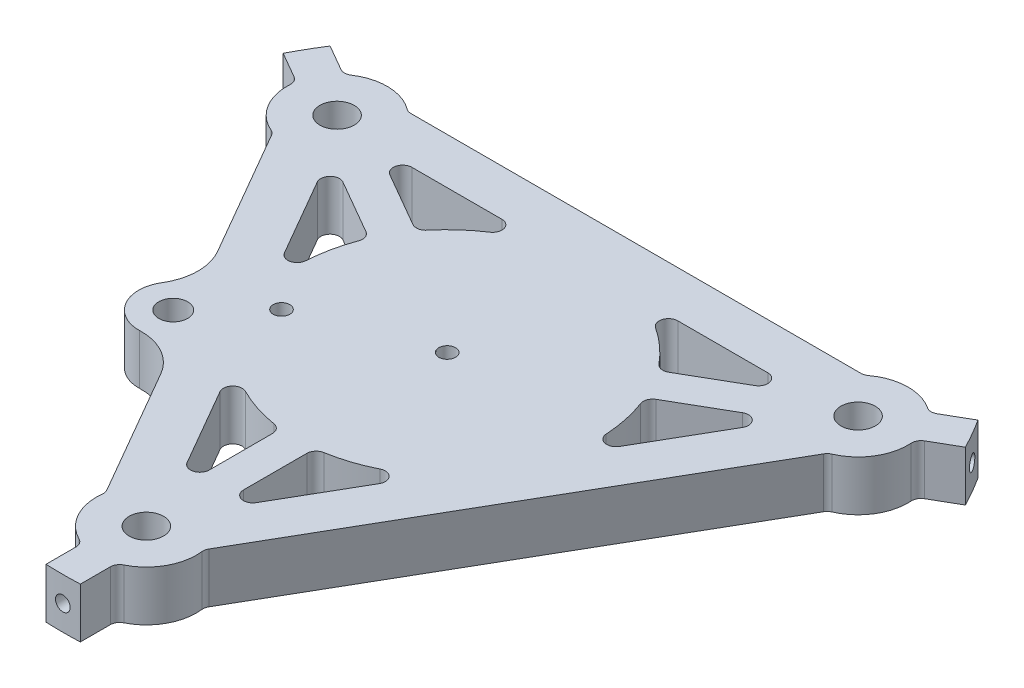
SolidWorks part; units mm, degrees
material "ABS"
ref_plane "Front Plane" through (0, 0, 0) normal (0, 0, 1) x (1, 0, 0)
ref_plane "Top Plane" through (0, 0, 0) normal (0, 1, 0) x (1, 0, 0)
ref_plane "Right Plane" through (0, 0, 0) normal (1, 0, 0) x (0, 0, -1)
sketch "Sketch1" plane through (0, 0, 0) normal (0, 1, 0) x (1, 0, 0)
  line L0 (-3.2639, -67.2662) -> (-3.2639, -72.952)
  line L1 (3.2639, -67.2662) -> (3.2639, -72.952)
  line L2 (3.2639, -41.9471) -> (3.2639, -29.9313)
  line L3 (-3.2639, -41.9471) -> (-3.2639, -29.9313)
  line L4 (-34.6953, 23.8002) -> (-24.2893, 17.7923)
  line L5 (-37.9592, 18.1469) -> (-27.5532, 12.139)
  line L6 (-56.6223, 36.4597) -> (-61.5464, 39.3026)
  line L7 (-59.8862, 30.8065) -> (-64.8103, 33.6494)
  line L8 (37.9592, 18.1469) -> (27.5532, 12.139)
  line L9 (34.6953, 23.8002) -> (24.2893, 17.7923)
  line L10 (59.8862, 30.8065) -> (64.8103, 33.6494)
  line L11 (56.6223, 36.4597) -> (61.5464, 39.3026)
  line L12 (0, 0) -> (0, -57.15) construction
  line L13 (0, 0) -> (-49.4934, 28.575) construction
  line L14 (0, 0) -> (49.4934, 28.575) construction
  line L15 (40.388, 15.7181) -> (31.8393, 0.9115)
  line L16 (9.6892, -54.9694) -> (52.4495, 19.0936)
  line L17 (-6.5817, -42.8361) -> (-15.1303, -28.0294)
  line L18 (-52.4495, 19.0936) -> (-9.6892, -54.9694)
  line L19 (-42.7603, 35.8758) -> (42.7603, 35.8758)
  line L20 (-33.8063, 27.118) -> (-16.709, 27.118)
  line L21 (16.709, 27.118) -> (33.8063, 27.118)
  line L22 (-31.8393, 0.9115) -> (-40.388, 15.7181)
  line L23 (15.1303, -28.0294) -> (6.5817, -42.8361)
  arc A0 (-3.2639, -72.952) -> (3.2639, -72.952) centre (0, 0) ccw
  arc A1 (4.7466, -28.178) -> (12.7944, -25.5506) centre (0, 0) ccw
  arc A2 (-9.4626, -56.0616) -> (-4.2488, -65.6749) centre (0, -57.15) ccw
  circle A3 centre (0, -57.15) radius 3.2639
  arc A4 (4.2488, -65.6749) -> (9.4626, -56.0616) centre (0, -57.15) ccw
  arc A5 (-43.8195, 36.2257) -> (-54.7517, 36.517) centre (-49.4934, 28.575) ccw
  arc A6 (-61.5464, 39.3026) -> (-64.8103, 33.6494) centre (0, 0) ccw
  arc A7 (-59.0005, 29.1579) -> (-53.2821, 19.8359) centre (-49.4934, 28.575) ccw
  circle A8 centre (-49.4934, 28.575) radius 3.2639
  arc A9 (53.2821, 19.8359) -> (59.0005, 29.1579) centre (49.4934, 28.575) ccw
  arc A10 (64.8103, 33.6494) -> (61.5464, 39.3026) centre (0, 0) ccw
  arc A11 (54.7517, 36.517) -> (43.8195, 36.2257) centre (49.4934, 28.575) ccw
  circle A12 centre (49.4934, 28.575) radius 3.2639
  arc A13 (-26.7762, 9.9784) -> (-28.5247, 1.695) centre (0, 0) ccw
  arc A14 (22.0296, 18.1997) -> (15.7302, 23.8556) centre (0, 0) ccw
  circle A15 centre (0, 0) radius 1.5875
  arc A16 (-12.7944, -25.5506) -> (-4.7466, -28.178) centre (0, 0) ccw
  arc A17 (28.5247, 1.695) -> (26.7762, 9.9784) centre (0, 0) ccw
  arc A18 (-15.7302, 23.8556) -> (-22.0296, 18.1997) centre (0, 0) ccw
  arc A19 (37.9592, 18.1469) -> (40.388, 15.7181) centre (38.8482, 16.6071) cw
  arc A20 (26.7762, 9.9784) -> (27.5532, 12.139) centre (28.4422, 10.5992) cw
  arc A21 (3.2639, -29.9313) -> (4.7466, -28.178) centre (5.0419, -29.9313) cw
  arc A22 (15.1303, -28.0294) -> (12.7944, -25.5506) centre (13.5905, -27.1404) ccw
  arc A23 (6.5817, -42.8361) -> (3.2639, -41.9471) centre (5.0419, -41.9471) cw
  arc A24 (-6.5817, -42.8361) -> (-3.2639, -41.9471) centre (-5.0419, -41.9471) ccw
  arc A25 (-3.2639, -29.9313) -> (-4.7466, -28.178) centre (-5.0419, -29.9313) ccw
  arc A26 (-15.1303, -28.0294) -> (-12.7944, -25.5506) centre (-13.5905, -27.1404) cw
  arc A27 (-31.8393, 0.9115) -> (-28.5247, 1.695) centre (-30.2996, 1.8005) ccw
  arc A28 (-26.7762, 9.9784) -> (-27.5532, 12.139) centre (-28.4422, 10.5992) ccw
  arc A29 (-40.388, 15.7181) -> (-37.9592, 18.1469) centre (-38.8482, 16.6071) cw
  arc A30 (-24.2893, 17.7923) -> (-22.0296, 18.1997) centre (-23.4003, 19.3321) ccw
  arc A31 (-34.6953, 23.8002) -> (-33.8063, 27.118) centre (-33.8063, 25.34) cw
  arc A32 (-15.7302, 23.8556) -> (-16.709, 27.118) centre (-16.709, 25.34) ccw
  arc A33 (-4.2488, -65.6749) -> (-3.2639, -67.2662) centre (-5.0419, -67.2662) cw
  arc A34 (3.2639, -67.2662) -> (4.2488, -65.6749) centre (5.0419, -67.2662) cw
  arc A35 (9.6892, -54.9694) -> (9.4626, -56.0616) centre (11.229, -55.8584) ccw
  arc A36 (-9.4626, -56.0616) -> (-9.6892, -54.9694) centre (-11.229, -55.8584) ccw
  arc A37 (-52.4495, 19.0936) -> (-53.2821, 19.8359) centre (-53.9893, 18.2046) ccw
  arc A38 (-59.0005, 29.1579) -> (-59.8862, 30.8065) centre (-60.7752, 29.2667) ccw
  arc A39 (-56.6223, 36.4597) -> (-54.7517, 36.517) centre (-55.7333, 37.9995) ccw
  arc A40 (-43.8195, 36.2257) -> (-42.7603, 35.8758) centre (-42.7603, 37.6538) ccw
  arc A41 (42.7603, 35.8758) -> (43.8195, 36.2257) centre (42.7603, 37.6538) ccw
  arc A42 (52.4495, 19.0936) -> (53.2821, 19.8359) centre (53.9893, 18.2046) cw
  arc A43 (54.7517, 36.517) -> (56.6223, 36.4597) centre (55.7333, 37.9995) ccw
  arc A44 (59.0005, 29.1579) -> (59.8862, 30.8065) centre (60.7752, 29.2667) cw
  arc A45 (15.7302, 23.8556) -> (16.709, 27.118) centre (16.709, 25.34) cw
  arc A46 (34.6953, 23.8002) -> (33.8063, 27.118) centre (33.8063, 25.34) ccw
  arc A47 (22.0296, 18.1997) -> (24.2893, 17.7923) centre (23.4003, 19.3321) ccw
  arc A48 (31.8393, 0.9115) -> (28.5247, 1.695) centre (30.2996, 1.8005) cw
  point P53 (18.9808, -21.3603)
  point P64 (-27.9889, -5.7577)
  point P77 (-3.2639, -66.0983)
  point P80 (3.2639, -66.0983)
  point P103 (9.0082, 27.118)
  dimension "D1" = 146.05
  dimension "D2" = 57.15
  dimension "D3" = 19.05
  dimension "D4" = 6.5278
  dimension "D9" = 3.175
  dimension "D10" = 1.778
  dimension "D11" = 1.778
  dimension "D5" = 57.15
  dimension "D7" = 120
  dimension "D8" = 120
  dimension "D6" = 3
extrude "Boss-Extrude1" add sketch "Sketch1" along normal mid plane 9.525
sketch "Sketch2" plane through (0, 0, 0) normal (0, 0, 1) x (1, 0, 0)
  line L0 (0, 4.7625) -> (0, -4.7625) construction
  line L1 (3.2639, 4.7625) -> (-3.2639, 4.7625) construction
  line L2 (-3.2639, -4.7625) -> (3.2639, -4.7625) construction
ref_plane "Plane1" through (0, 0, 73.025) normal (0, 0, 1) x (1, 0, 0)
sketch "Sketch3" plane through (0, 0, 73.025) normal (0, 0, 1) x (1, 0, 0)
  circle A0 centre (0, 0) radius 1.397
  dimension "D1" = 2.794
extrude "Cut-Extrude1" cut sketch "Sketch3" against normal blind 6.35
pattern_circular "CirPattern1" count 3 over 360 about axis through (0, 4.7625, 0) along (0, -1, 0) of "Cut-Extrude1"
sketch "Sketch4" plane through (0, -4.7625, 0) normal (0, -1, 0) x (1, 0, 0)
  circle A0 centre (-22.821, 8.6514) radius 1.5875
  dimension "D1" = 3.175
extrude "Cut-Extrude2" cut sketch "Sketch4" against normal through all both and the other way through all
sketch "Sketch5" plane through (0, 4.7625, 0) normal (0, 1, 0) x (1, 0, 0)
  line L0 (0, 0) -> (-32.9956, -19.05)
  line L1 (-52.4495, 19.0936) -> (-9.6892, -54.9694) construction
  line L2 (-52.4495, 19.0936) -> (-9.6892, -54.9694)
  circle A0 centre (-32.9956, -19.05) radius 2.75
  circle A1 centre (-32.9956, -19.05) radius 6.56
  dimension "D2" = 5.5
  dimension "D1" = 38.1
  dimension "D3" = 3.81
extrude "Boss-Extrude2" add sketch "Sketch5" against normal up to surface (9.525 mm away) contours L2 A1 A0 region at (-33.1673, 4.7625, 14.6524) up to face at (-22.821, -4.7625, 10.2389)
extrude "Cut-Extrude3" cut sketch "Sketch5<3>" against normal through all contours L2 A0 L0 | L0 A0 L2 region at (-30.5781, 4.7625, 18.3644) region at (-31.1931, 4.7625, 17.2992)
sketch "Sketch5<3>" plane through (0, 4.7625, 0) normal (0, 1, 0) x (1, 0, 0) same geometry as "Sketch5"
fillet "Fillet2" radius 10.16 2 edges at (-34.1551, 0, 12.5933) (-27.9836, 0, 23.2825)
equation "\"Bodytube_OD\" = 6.17in"
equation "\"Bodytube_ID\" = 5.998in"
equation "\"Motor_OD\" = 4in"
equation "\"Fwd_Tube_Length\" = 38in"
equation "\"Mid_Tube_Length\" = 8in"
equation "\"Aft_Section_Length\"= 40in"
equation "\"Mid_Coupler_Length\"= 13in"
equation "\"Aft_Lower_Length\"= 22in"
equation "\"AB_Coupler_OD_Length\"= 1in"
equation "\"AB_Coupling_Section_Length\"= 0.375in"
equation "\"AB_Coupler_Length\"= \"AB_Coupler_OD_Length\" + \"AB_Coupling_Section_Length\" * 2"
equation "\"Cutout_Angle\" = 80"
equation "\"AB_Paddle_Height\" = 0.375in"
equation "\"AB_Coupler_Num_Screws\"= 6"
equation "\"Num_Cutouts\" = 3"
equation "\"AB_Coupler_OD\"= 6.17in"
equation "\"AB_Coupler_ID\"= 5.75in"
equation "\"AB_Coupler_Surface_Diameter\"= 5.998in"
equation "\"AB_Coupling_Screw_Diameter\"= 0.1065in"
equation "\"AB_Central_Bushing_Length\" = .75in"
equation "\"Lead_Screw_Dist\" = 2.25in"
equation "\"Lead_Screw_Diam\" = (27/64)*1in"
equation "\"Lead_Screw_Length\" = (\"Mid_Coupler_Length\" + 2*0.375in + 2*0.5in)"
equation "\"Paddle_Pin_Offset\" = .25in"
equation "\"Paddle_Pin_Radius\" = 2.25in"
equation "\"Paddle_Gear_OD\" = 3.2in"
equation "\"Fwd_BKHD_From_Top\" = 18in"
equation "\"Fin_Thickness\"= .118in"
equation "\"Guiderail_Cutout_Diameter\"= 1.5in"
equation "\"D5@Sketch1\"=\"Paddle_Pin_Radius\""
